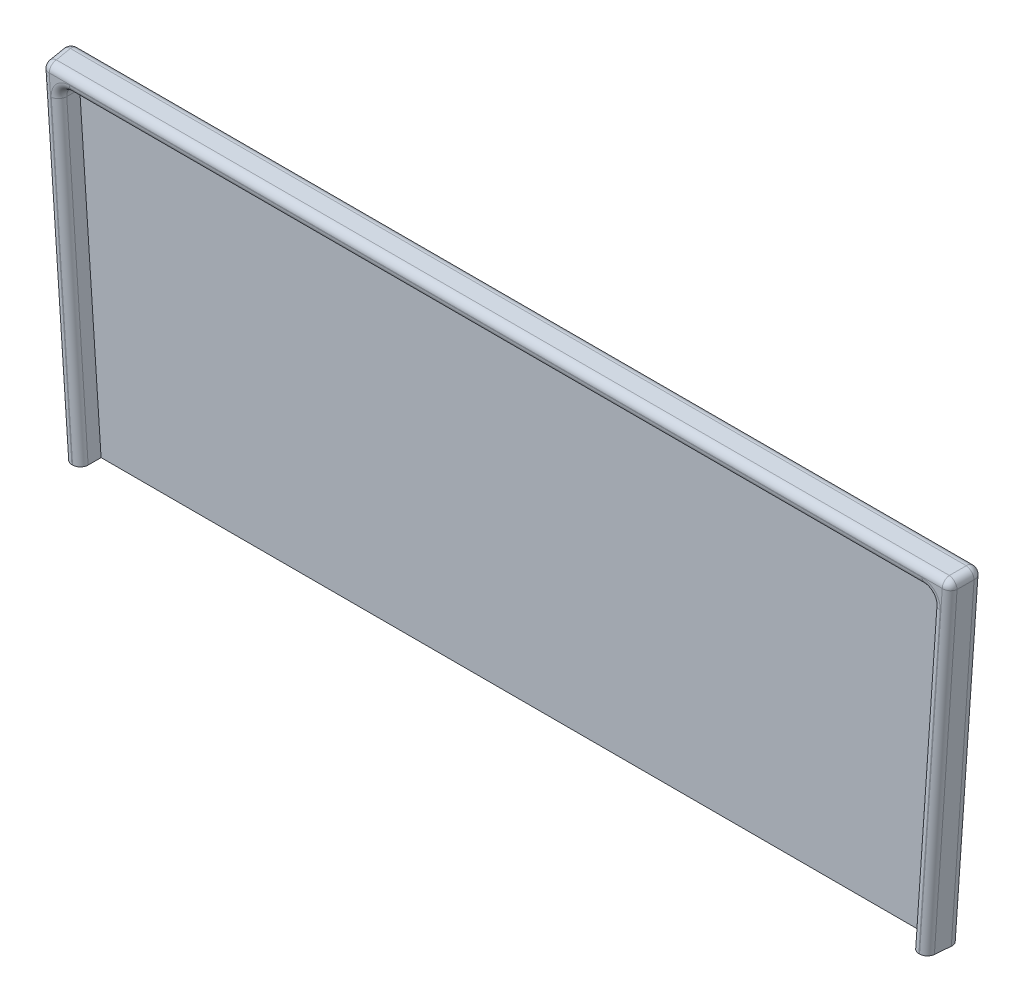
SolidWorks part; units mm, degrees
ref_plane "前视基准面" through (0, 0, 0) normal (0, 0, 1) x (1, 0, 0)
ref_plane "上视基准面" through (0, 0, 0) normal (0, 1, 0) x (1, 0, 0)
ref_plane "右视基准面" through (0, 0, 0) normal (1, 0, 0) x (0, 0, -1)
sketch "草图1" plane through (0, 0, 0) normal (0, 0, 1) x (1, 0, 0)
  line L0 (0, 0) -> (0, 32.5) construction
  line L1 (-44, 32.5) -> (44, 32.5) construction
  line L2 (-41.75, 0) -> (41.75, 0) construction
  line L3 (44, 32.5) -> (41.75, 0) construction
  line L4 (-44, 32.5) -> (-41.75, 0) construction
  line L5 (-41.75, 0) -> (-41.0577, -10) construction
  line L6 (-41.0577, -10) -> (41.0577, -10) construction
  line L7 (41.0577, -10) -> (41.75, 0) construction
  line L8 (-44.1072, 32.6) -> (-41.8498, -0.0069)
  line L9 (-41.8498, -0.0069) -> (-41.151, -10.1)
  line L10 (-41.151, -10.1) -> (41.151, -10.1)
  line L11 (41.151, -10.1) -> (41.8498, -0.0069)
  line L12 (44.1072, 32.6) -> (41.8498, -0.0069)
  line L13 (-44.1072, 32.6) -> (44.1072, 32.6)
  point P0 (0, 0)
  point P7 (0, 0)
  point P10 (0, 32.5)
  dimension "D1" = 32.5
  dimension "D2" = 83.5
  dimension "D3" = 88
  dimension "D4" = 10
  dimension "D5" = 0.1
extrude "凸台-拉伸2" add sketch "草图1" along normal blind 3 draft 5
sketch "草图2" plane through (0, 0, 0) normal (0, 1, 0) x (1, 0, 0)
  line L1 (-45, 0) -> (45, 0)
  line L2 (-45, 0) -> (-45, -5)
  line L3 (-45, -5) -> (45, -5)
  line L4 (45, 0) -> (45, -5)
  dimension "D1" = 90
  dimension "D2" = 5
extrude "切除-拉伸1" cut sketch "草图2" against normal through all
sketch "草图3" plane through (0, 0, 3) normal (0, 0, 1) x (1, 0, 0)
  line L0 (-41.5871, 0) -> (41.5871, 0) construction
  line L10 (-40.0836, 0) -> (40.0836, 0)
  line L13 (40.0907, 0.1036) -> (42.2185, 30.8375)
  line L14 (42.2185, 30.8375) -> (-42.2185, 30.8375)
  line L15 (-42.2185, 30.8375) -> (-40.0907, 0.1036)
  line L16 (40.0836, 0) -> (42.2185, 30.8375)
  line L17 (42.2185, 30.8375) -> (-42.2185, 30.8375)
  line L18 (-42.2185, 30.8375) -> (-40.0836, 0)
  dimension "D1" = 1.5
extrude "切除-拉伸2" cut sketch "草图3" against normal blind 2
fillet "圆角3" radius 0.75 2 edges at (-43.9665, 32.4688, 1.5) (43.9665, 32.4688, 1.5)
fillet "圆角1" radius 1 2 edges at (42.2185, 30.8375, 2) (-42.2185, 30.8375, 2)
fillet "圆角2" radius 0.75 5 edges at (41.114, 14.8842, 3) (41.878, 30.5198, 3) (-41.114, 14.8842, 3) (-41.878, 30.5198, 3) (0, 30.8375, 3)
fillet "圆角4" radius 0.75 5 edges at (42.6789, 15.7694, 3) (43.5719, 32.1005, 3) (0, 32.3375, 3) (-43.5719, 32.1005, 3) (-42.6789, 15.7694, 3)
fillet "圆角5" radius 0.75 5 edges at (42.9511, 15.9006, 0) (43.8532, 32.363, 0) (0, 32.6, 0) (-43.8532, 32.363, 0) (-42.9511, 15.9006, 0)
